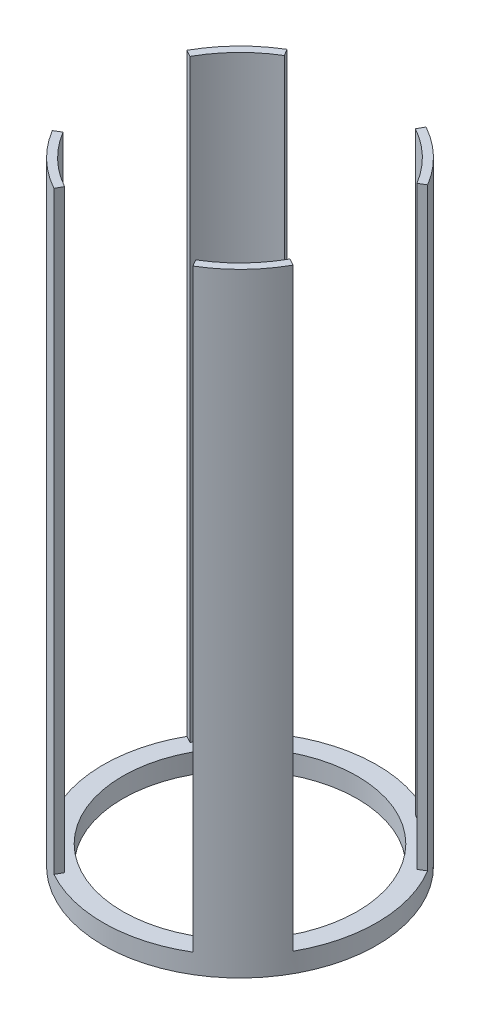
SolidWorks part; units mm, degrees
material "6061-T6 (SS)"
ref_plane "Front Plane" through (0, 0, 0) normal (0, 0, 1) x (1, 0, 0)
ref_plane "Top Plane" through (0, 0, 0) normal (0, 1, 0) x (1, 0, 0)
ref_plane "Right Plane" through (0, 0, 0) normal (1, 0, 0) x (0, 0, -1)
sketch "Sketch2" plane through (0, 0, 0) normal (0, 1, 0) x (1, 0, 0)
  circle A0 centre (0, 0) radius 88.9
  circle A1 centre (0, 0) radius 83.82
  dimension "D1" = 177.8
  dimension "D2" = 167.64
extrude "Boss-Extrude1" add sketch "Sketch2" along normal mid plane 398.78
sketch "Sketch3" plane through (0, 0, 0) normal (0, 1, 0) x (1, 0, 0)
  line L0 (0, 0) -> (169.6618, 101.6776)
  line L1 (-58.1167, 96.9749) -> (0, 0)
  line L2 (0, 0) -> (53.9, 96.9749)
  line L3 (53.9, 96.9749) -> (-58.1167, 96.9749)
  line L4 (0, 0) -> (70.9917, -118.4586)
  line L5 (70.9917, -118.4586) -> (-65.8409, -118.4586)
  line L6 (-65.8409, -118.4586) -> (0, 0)
  line L7 (169.6618, 101.6776) -> (169.6618, -94.3004)
  line L8 (169.6618, -94.3004) -> (0, 0)
  line L9 (0, 0) -> (-123.7413, 68.7771)
  line L10 (-123.7413, 68.7771) -> (-123.7413, -74.1577)
  line L11 (-123.7413, -74.1577) -> (0, 0)
  dimension "D1" = 60
  dimension "D2" = 60
  dimension "D3" = 60
  dimension "D4" = 60
  dimension "D5" = 30
  dimension "D6" = 30
extrude "Cut-Extrude1" cut sketch "Sketch3" against normal through all both and the other way through all contours L8 L7 L0 | L2 L3 L1 | L10 L11 L9 | L6 L5 L4 region at (-1.4056, 0, -64.65) region at (1.7169, 0, 78.9724) region at (113.1078, 0, -2.4591) region at (-82.4942, 0, 1.7935)
sketch "Sketch4" plane through (0, -199.39, 0) normal (0, -1, 0) x (1, 0, 0)
  circle A0 centre (0, 0) radius 88.9
  circle A1 centre (0, 0) radius 76.2
  dimension "D1" = 152.4
  dimension "D2" = 177.8
extrude "Boss-Extrude2" add sketch "Sketch4" against normal blind 12.7
equation "\"D1@Boss-Extrude1\"=3*12"
